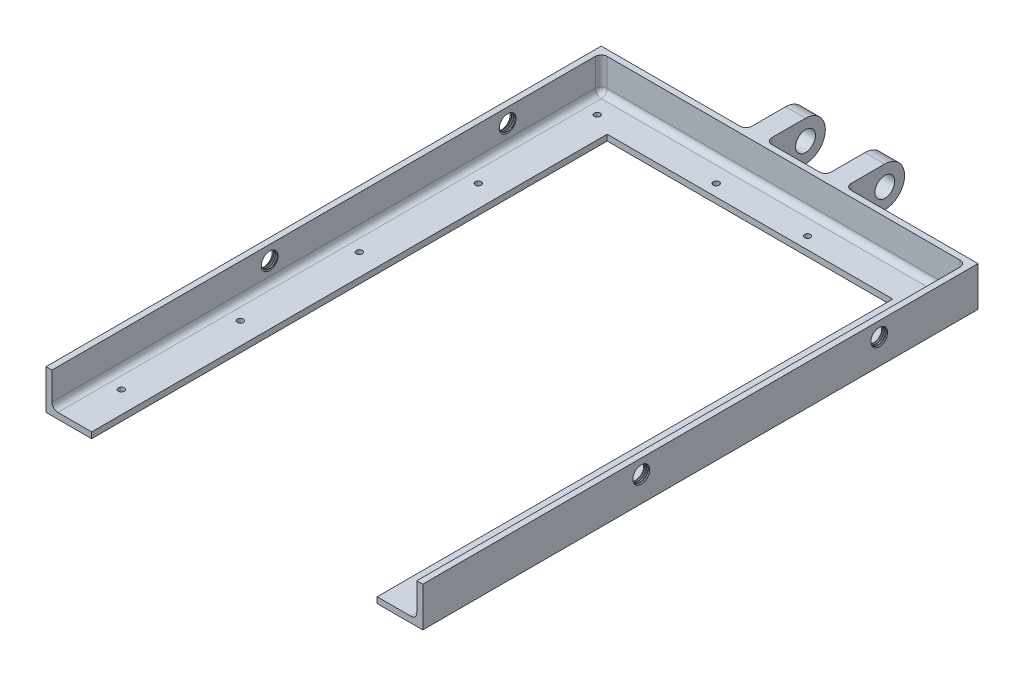
SolidWorks part; units mm, degrees
ref_plane "Front Plane" through (0, 0, 0) normal (0, 0, 1) x (1, 0, 0)
ref_plane "Top Plane" through (0, 0, 0) normal (0, 1, 0) x (1, 0, 0)
ref_plane "Right Plane" through (0, 0, 0) normal (1, 0, 0) x (0, 0, -1)
sketch "Sketch1" plane through (0, 0, 0) normal (0, 1, 0) x (1, 0, 0)
  line L1 (-98, -10) -> (98, -10)
  line L2 (-98, -10) -> (-98, 10)
  line L3 (-98, 10) -> (98, 10)
  line L4 (98, -10) -> (98, 10)
  line L5 (-98, -10) -> (98, 10) construction
  line L6 (-98, 10) -> (98, -10) construction
  point P0 (0, 0)
  dimension "D1" = 20
  dimension "D2" = 196
extrude "Boss-Extrude1" add sketch "Sketch1" along normal blind 3
sketch "Sketch2" plane through (0, 3, 0) normal (0, 1, 0) x (1, 0, 0)
  line L0 (98, -10) -> (98, 10) construction
  line L1 (-98, 10) -> (98, 10)
  line L2 (-98, 10) -> (-98, 7)
  line L3 (-98, 7) -> (98, 7)
  line L4 (98, 10) -> (98, 7)
  dimension "D1" = 3
extrude "Boss-Extrude2" add sketch "Sketch2" along normal blind 17
fillet "Fillet1" radius 3 1 edges at (0, 3, -7)
sketch "Sketch4" plane through (0, 0, -10) normal (0, 0, -1) x (-1, 0, 0)
  line L0 (-98, 0) -> (98, 0) construction
  line L1 (-25, 20) -> (-15, 20)
  line L2 (-25, 20) -> (-25, 0)
  line L3 (-25, 0) -> (-15, 0)
  line L4 (-15, 20) -> (-15, 0)
  line L9 (0, 0) -> (0, 7.6019) construction
  line L11 (15, 20) -> (15, 0)
  line L12 (25, 0) -> (15, 0)
  line L13 (25, 20) -> (25, 0)
  line L14 (25, 20) -> (15, 20)
  dimension "D1" = 20
  dimension "D2" = 10
  dimension "D3" = 15
extrude "Boss-Extrude3" add sketch "Sketch4" along normal blind 30
sketch "Sketch5" plane through (15, 0, 0) normal (-1, 0, 0) x (0, 0, 1)
  line L0 (-40, 0) -> (-40, 20) construction
  line L1 (-40, 0) -> (-10, 0) construction
  circle A0 centre (-30, 10) radius 5
  dimension "D1" = 10
  dimension "D2" = 10
  dimension "D3" = 10
fillet "Fillet2" radius 10 4 edges at (-20, 0, -40) (-20, 20, -40) (20, 0, -40) (20, 20, -40)
extrude "Cut-Extrude2" cut sketch "Sketch5" against normal through all both and the other way through all contours A0
sketch "Sketch6" plane through (0, 0, 10) normal (0, 0, 1) x (1, 0, 0)
  line L0 (-98, 20) -> (98, 20) construction
  line L1 (-98, 0) -> (-75, 0)
  line L2 (-98, 0) -> (-98, 20)
  line L3 (-98, 20) -> (-95, 20)
  line L4 (-95, 3) -> (-95, 20)
  line L10 (-98, 3) -> (-98, 0) construction
  line L11 (-98, 0) -> (98, 0) construction
  line L13 (-75, 0) -> (-75, 3)
  line L14 (98, 3) -> (-98, 3) construction
  line L15 (-75, 3) -> (-95, 3)
  dimension "D1" = 3
  dimension "D2" = 20
extrude "Boss-Extrude4" add sketch "Sketch6" along normal blind 277 from surface starting at face at (0, 13, -7)
sketch "Sketch7" plane through (0, 0, 10) normal (0, 0, 1) x (1, 0, 0)
  line L0 (-75, 0) -> (98, 0) construction
  line L1 (92, 0) -> (87, 0)
  line L2 (92, 0) -> (92, 20)
  line L3 (92, 20) -> (89, 20)
  line L4 (89, 3) -> (89, 20)
  line L5 (-95, 20) -> (98, 20) construction
  line L6 (98, 3) -> (98, 0) construction
  line L7 (87, 0) -> (69, 0)
  line L8 (-75, 0) -> (98, 0) construction
  line L9 (69, 0) -> (69, 3)
  line L10 (-75, 3) -> (98, 3) construction
  line L11 (69, 3) -> (89, 3)
  dimension "D1" = 5
  dimension "D2" = 6
  dimension "D3" = 20
  dimension "D4" = 3
  dimension "D5" = 6
extrude "Boss-Extrude5" add sketch "Sketch7" along normal blind 277 from surface starting at face at (1.5, 13, -7)
sketch "Sketch8" plane through (0, 0, 10) normal (0, 0, 1) x (1, 0, 0)
  line L0 (98, 20) -> (98, 6) construction
  line L1 (98, 0) -> (92, 0)
  line L2 (98, 0) -> (98, 26.1425)
  line L3 (98, 26.1425) -> (92, 26.1425)
  line L4 (92, 0) -> (92, 26.1425)
extrude "Cut-Extrude3" cut sketch "Sketch8" against normal blind 30
sketch "Sketch9" plane through (0, 3, 0) normal (0, 1, 0) x (1, 0, 0)
  line L1 (-95, -270) -> (-95, 4) construction
  line L2 (89, -270) -> (89, 4) construction
  line L3 (-95, 7) -> (89, 7) construction
  line L6 (-95, 7) -> (89, 7) construction
  circle A0 centre (-86, -4) radius 1.5
  circle A1 centre (-26, -4) radius 1.5
  circle A2 centre (20, -4) radius 1.5
  circle A3 centre (80, -4) radius 1.5
  circle A5 centre (-86, -64) radius 1.5
  circle A6 centre (-86, -124) radius 1.5
  circle A7 centre (80, -64) radius 1.5
  circle A9 centre (80, -124) radius 1.5
  circle A10 centre (-86, -184) radius 1.5
  circle A11 centre (80, -184) radius 1.5
  circle A12 centre (-86, -244) radius 1.5
  circle A13 centre (80, -244) radius 1.5
  dimension "D3" = 3
  dimension "D9" = 60
  dimension "D10" = 166
  dimension "D11" = 60
  dimension "D13" = 60
  dimension "D1" = 11
  dimension "D2" = 9
  dimension "D5" = 9
  dimension "D6" = 60
  dimension "D7" = 11
  dimension "D8" = 11
  dimension "D4" = 2
  dimension "D12" = 2
  dimension "D14" = 3
extrude "Cut-Extrude4" cut sketch "Sketch9" against normal through all
fillet "Fillet4" radius 3 6 edges at (89, 13, -7) (89, 3.8787, -6.1213) (-95, 13, -7) (-95, 3.8787, -6.1213) (89, 3, 133) (-95, 3, 133)
sketch "Sketch10" plane through (-98, 0, 0) normal (-1, 0, 0) x (0, 0, 1)
  line L0 (-10, 20) -> (270, 20) construction
  line L1 (270, 0) -> (270, 20) construction
  circle A0 centre (160, 13) radius 4
  circle A1 centre (40, 13) radius 4
  dimension "D2" = 110
  dimension "D3" = 8
  dimension "D1" = 7
  dimension "D4" = 2
extrude "Cut-Extrude5" cut sketch "Sketch10" against normal up to surface (190 mm away) up to face at (92, 10, 130)
thread "Thread1" pitch 1 method cut profile "Thread Profile1" start angle 0, offset 1, length 10, pitch 1, diameter 8
ref_plane "Plane1" through (-99, 13, 36) normal (0, -1, 0) x (0, 0, -1)
sketch "Thread Profile1" plane through (-99, 13, 36) normal (0, -1, 0) x (0, 0, -1)
  line L0 (0, 0) -> (0, 1) construction
  line L1 (0, 0) -> (0.5413, 0.3125)
  line L2 (0.5413, 0.3125) -> (0.5413, 0.4375)
  line L3 (0.5413, 0.4375) -> (0, 0.75)
  line L4 (0.5413, 0.375) -> (0, 0.375) construction
  line L11 (0, 0) -> (0, 0.75)
  point P2 (0, 0)
  dimension "Pitch" = 1
  dimension "Profile_Angle" = 60
  dimension "Profile_Land" = 0.125
  dimension "Profile_Height" = 0.5413
thread "Thread2" pitch 1 method cut profile "Thread Profile2" start angle 0, offset 1, length 10, pitch 1, diameter 8
ref_plane "Plane2" through (-99, 13, 156) normal (0, -1, 0) x (0, 0, -1)
sketch "Thread Profile2" plane through (-99, 13, 156) normal (0, -1, 0) x (0, 0, -1)
  line L0 (0, 0) -> (0, 1) construction
  line L1 (0, 0) -> (0.5413, 0.3125)
  line L2 (0.5413, 0.3125) -> (0.5413, 0.4375)
  line L3 (0.5413, 0.4375) -> (0, 0.75)
  line L4 (0.5413, 0.375) -> (0, 0.375) construction
  line L11 (0, 0) -> (0, 0.75)
  point P2 (0, 0)
  dimension "Pitch" = 1
  dimension "Profile_Angle" = 60
  dimension "Profile_Land" = 0.125
  dimension "Profile_Height" = 0.5413
thread "Thread3" pitch 1 method cut profile "Thread Profile3" start angle 0, offset 1, length 10, pitch 1, diameter 8
ref_plane "Plane3" through (93, 13, 164) normal (0, -1, 0) x (0, 0, 1)
sketch "Thread Profile3" plane through (93, 13, 164) normal (0, -1, 0) x (0, 0, 1)
  line L0 (0, 0) -> (0, 1) construction
  line L1 (0, 0) -> (0.5413, 0.3125)
  line L2 (0.5413, 0.3125) -> (0.5413, 0.4375)
  line L3 (0.5413, 0.4375) -> (0, 0.75)
  line L4 (0.5413, 0.375) -> (0, 0.375) construction
  line L11 (0, 0) -> (0, 0.75)
  point P2 (0, 0)
  dimension "Pitch" = 1
  dimension "Profile_Angle" = 60
  dimension "Profile_Land" = 0.125
  dimension "Profile_Height" = 0.5413
thread "Thread4" pitch 1 method cut profile "Thread Profile4" start angle 0, offset 1, length 10, pitch 1, diameter 8
ref_plane "Plane4" through (93, 13, 44) normal (0, -1, 0) x (0, 0, 1)
sketch "Thread Profile4" plane through (93, 13, 44) normal (0, -1, 0) x (0, 0, 1)
  line L0 (0, 0) -> (0, 1) construction
  line L1 (0, 0) -> (0.5413, 0.3125)
  line L2 (0.5413, 0.3125) -> (0.5413, 0.4375)
  line L3 (0.5413, 0.4375) -> (0, 0.75)
  line L4 (0.5413, 0.375) -> (0, 0.375) construction
  line L11 (0, 0) -> (0, 0.75)
  point P2 (0, 0)
  dimension "Pitch" = 1
  dimension "Profile_Angle" = 60
  dimension "Profile_Land" = 0.125
  dimension "Profile_Height" = 0.5413
fillet "Fillet7" radius 3 4 edges at (-25, 10, -10) (-15, 10, -10) (15, 10, -10) (25, 10, -10)
